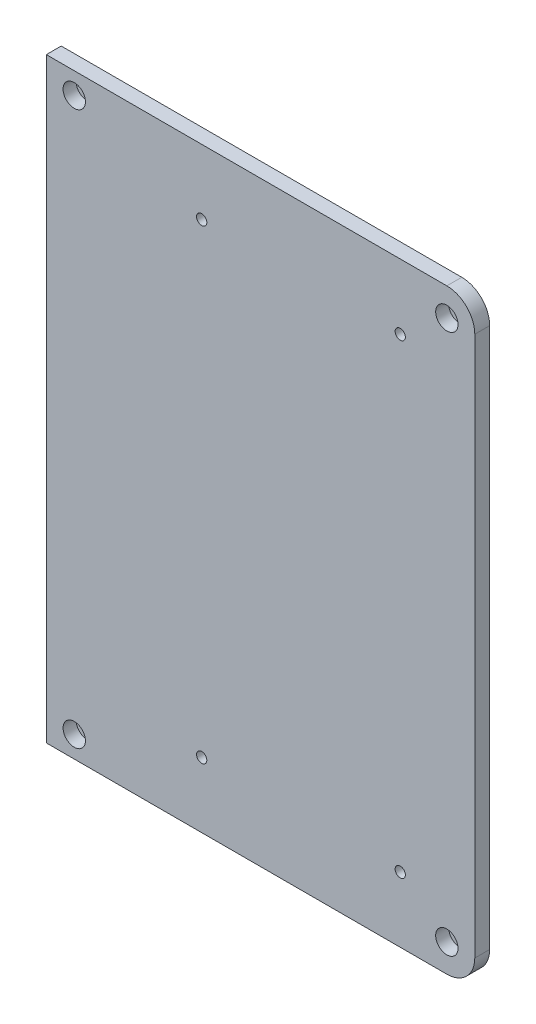
SolidWorks part; units mm, degrees
ref_plane "Front Plane" through (0, 0, 0) normal (0, 0, 1) x (1, 0, 0)
ref_plane "Top Plane" through (0, 0, 0) normal (0, 1, 0) x (1, 0, 0)
ref_plane "Right Plane" through (0, 0, 0) normal (1, 0, 0) x (0, 0, -1)
sketch "Sketch1" plane through (0, 0, 0) normal (0, 0, 1) x (1, 0, 0)
  line L1 (-107.5, 80) -> (107.5, 80)
  line L2 (-115, 72.5) -> (-115, -72.5)
  line L3 (-107.5, -80) -> (107.5, -80)
  line L4 (115, 72.5) -> (115, -72.5)
  line L5 (-115, 80) -> (115, -80) construction
  line L6 (-115, -80) -> (115, 80) construction
  arc A0 (-115, -72.5) -> (-107.5, -80) centre (-107.5, -72.5) ccw
  arc A1 (107.5, -80) -> (115, -72.5) centre (107.5, -72.5) ccw
  arc A2 (107.5, 80) -> (115, 72.5) centre (107.5, 72.5) cw
  arc A3 (-107.5, 80) -> (-115, 72.5) centre (-107.5, 72.5) ccw
  point P0 (0, 0)
  dimension "D3" = 7.5
  dimension "D1" = 230
  dimension "D2" = 160
extrude "Boss-Extrude1" add sketch "Sketch1" along normal blind 4
sketch "Sketch2" plane through (0, 0, 4) normal (0, 0, 1) x (1, 0, 0)
  line L0 (-115, 72.5) -> (-115, -72.5) construction
  line L1 (-107.5, -80) -> (107.5, -80) construction
  line L2 (107.5, 80) -> (-107.5, 80) construction
  line L3 (115, -72.5) -> (115, 72.5) construction
  circle A0 centre (-107.5, -72.5) radius 1.75
  circle A1 centre (-107.5, 72.5) radius 1.75
  circle A2 centre (107.5, -72.5) radius 1.75
  circle A3 centre (107.5, 72.5) radius 1.75
  dimension "D1" = 7.5
  dimension "D3" = 3.5
  dimension "D4" = 3.5
  dimension "D7" = 3.5
  dimension "D10" = 3.5
  dimension "D2" = 7.5
  dimension "D5" = 7.5
  dimension "D6" = 7.5
  dimension "D8" = 7.5
  dimension "D9" = 7.5
  dimension "D11" = 7.5
  dimension "D12" = 7.5
extrude "Cut-Extrude1" cut sketch "Sketch2" against normal blind 10
sketch "Sketch3" plane through (0, 0, 4) normal (0, 0, 1) x (1, 0, 0)
  circle A0 centre (-107.5, -72.5) radius 3
  circle A1 centre (-107.5, 72.5) radius 3
  circle A2 centre (107.5, 72.5) radius 3
  circle A3 centre (107.5, -72.5) radius 3
  dimension "D1" = 6
  dimension "D2" = 6
  dimension "D3" = 6
  dimension "D4" = 6
extrude "Cut-Extrude2" cut sketch "Sketch3" against normal blind 3.5
sketch "Sketch4" plane through (0, 0, 4) normal (0, 0, 1) x (1, 0, 0)
  line L0 (107.5, 80) -> (-107.5, 80) construction
  line L3 (-115, 72.5) -> (-115, -72.5) construction
  line L4 (-107.5, -80) -> (107.5, -80) construction
  circle A0 centre (-96.5, 37.5) radius 1.5
  circle A1 centre (-96.5, -37.5) radius 1.5
  circle A2 centre (-24.5, 37.5) radius 1.5
  circle A3 centre (-24.5, -37.5) radius 1.5
  dimension "D2" = 3
  dimension "D3" = 3
  dimension "D6" = 3
  dimension "D7" = 3
  dimension "D1" = 75
  dimension "D4" = 42.5
  dimension "D5" = 18.5
  dimension "D8" = 72
  dimension "D9" = 72
  dimension "D10" = 42.5
  dimension "D11" = 42.5
extrude "Cut-Extrude3" cut sketch "Sketch4" against normal through all
sketch "Sketch5" plane through (0, 0, 4) normal (0, 0, 1) x (1, 0, 0)
  line L0 (-107.5, -80) -> (107.5, -80) construction
  line L2 (115, -72.5) -> (115, 72.5) construction
  circle A0 centre (95, -62.5) radius 1.375
  circle A1 centre (95, 62.5) radius 1.375
  circle A2 centre (41.7, -62.5) radius 1.375
  circle A3 centre (41.7, 62.5) radius 1.375
  dimension "D1" = 125
  dimension "D4" = 2.75
  dimension "D6" = 53.3
  dimension "D2" = 17.5
  dimension "D3" = 20
  dimension "D5" = 53.3
extrude "Cut-Extrude4" cut sketch "Sketch5" against normal through all and the other way through all
sketch "Sketch7" plane through (0, 0, 4) normal (0, 0, 1) x (1, 0, 0)
  circle A0 centre (-102.8, 42.3) radius 1.5
  circle A1 centre (-96.5, 37.5) radius 1.5 construction
  circle A2 centre (-102.8, -42.3) radius 1.5
  circle A3 centre (-18.2, -42.3) radius 1.5
  circle A4 centre (-18.2, 42.3) radius 1.5
  circle A5 centre (-96.5, -37.5) radius 1.5 construction
  circle A6 centre (-24.5, -37.5) radius 1.5 construction
  circle A7 centre (-24.5, 37.5) radius 1.5 construction
  dimension "D1" = 6.3
  dimension "D3" = 3
  dimension "D4" = 3
  dimension "D5" = 3
  dimension "D6" = 3
  dimension "D7" = 4.8
  dimension "D8" = 6.3
  dimension "D10" = 4.8
  dimension "D11" = 4.8
  dimension "D12" = 6.3
  dimension "D2" = 4.8
extrude "Cut-Extrude6" cut sketch "Sketch7" against normal through all
sketch "Sketch8" plane through (0, 0, 0) normal (0, 0, -1) x (-1, 0, 0)
  circle A0 centre (18.2, 42.3) radius 3
  circle A1 centre (18.2, -42.3) radius 3
  circle A2 centre (102.8, -42.3) radius 3
  circle A3 centre (102.8, 42.3) radius 3
  dimension "D1" = 6
  dimension "D2" = 6
  dimension "D3" = 6
  dimension "D4" = 6
extrude "Cut-Extrude7" cut sketch "Sketch8" against normal blind 3.5
sketch "Sketch9" plane through (0, 0, 4) normal (0, 0, 1) x (1, 0, 0)
  line L0 (115, -72.5) -> (115, 72.5) construction
  line L1 (-115, 80) -> (0, 80)
  line L2 (-115, 80) -> (-115, -80)
  line L3 (-115, -80) -> (0, -80)
  line L4 (0, 80) -> (0, -80)
  line L5 (107.5, 80) -> (-107.5, 80) construction
  line L6 (-107.5, -80) -> (107.5, -80) construction
  line L7 (-115, 72.5) -> (-115, -72.5) construction
  dimension "D1" = 115
  dimension "D2" = 0
  dimension "D3" = 0
  dimension "D4" = 0
extrude "Cut-Extrude8" cut sketch "Sketch9" against normal blind 10
sketch "Sketch10" plane through (0, 0, 4) normal (0, 0, 1) x (1, 0, 0)
  line L1 (0, -80) -> (107.5, -80) construction
  line L2 (0, -80) -> (0, 80) construction
  circle A0 centre (7.5, -74.25) radius 1.75
  dimension "D1" = 3.5
  dimension "D2" = 7.5
  dimension "D3" = 5.75
extrude "Cut-Extrude9" cut sketch "Sketch10" against normal up to surface (4 mm away) up to face at (96.375, 62.5, 0)
sketch "Sketch14" plane through (0, 0, 4) normal (0, 0, 1) x (1, 0, 0)
  line L1 (0, -80) -> (107.5, -80) construction
  line L2 (0, -80) -> (0, 80) construction
  circle A0 centre (7.5, -74.25) radius 3
  dimension "D3" = 6
  dimension "D1" = 7.5
  dimension "D2" = 5.75
extrude "Cut-Extrude10" cut sketch "Sketch14" against normal blind 3.5
sketch "Sketch16" plane through (0, 0, 4) normal (0, 0, 1) x (1, 0, 0)
  line L0 (107.5, 80) -> (0, 80) construction
  line L2 (0, -80) -> (0, 80) construction
  circle A0 centre (7.5, 74.25) radius 1.75
  dimension "D3" = 3.5
  dimension "D1" = 5.75
  dimension "D2" = 7.5
extrude "Cut-Extrude11" cut sketch "Sketch16" against normal up to surface (4 mm away) up to face at (9.25, -74.25, 0)
sketch "Sketch17" plane through (0, 0, 4) normal (0, 0, 1) x (1, 0, 0)
  line L0 (107.5, 80) -> (0, 80) construction
  line L2 (0, -80) -> (0, 80) construction
  circle A0 centre (7.5, 74.25) radius 3
  dimension "D1" = 6
  dimension "D2" = 5.75
  dimension "D3" = 7.5
extrude "Cut-Extrude12" cut sketch "Sketch17" against normal blind 3.5
